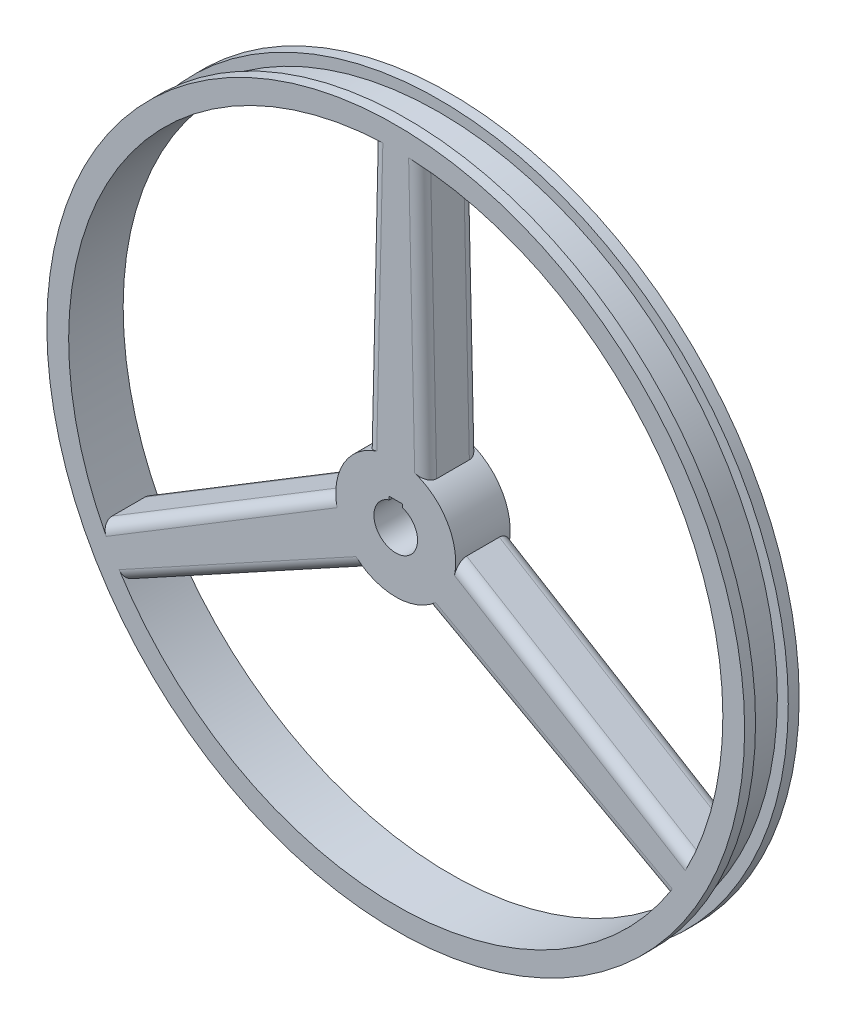
SolidWorks part; units mm, degrees
ref_plane "前视基准面" through (0, 0, 0) normal (0, 0, 1) x (1, 0, 0)
ref_plane "上视基准面" through (0, 0, 0) normal (0, 1, 0) x (1, 0, 0)
ref_plane "右视基准面" through (0, 0, 0) normal (1, 0, 0) x (0, 0, -1)
sketch "草图1" plane through (0, 0, 0) normal (0, 0, 1) x (1, 0, 0)
  circle A0 centre (0, 0) radius 320
  circle A1 centre (0, 0) radius 300
  dimension "D1" = 600
  dimension "D2" = 640
extrude "凸台-拉伸1" add sketch "草图1" along normal blind 50
sketch "草图2" plane through (0, 0, 0) normal (0, 0, 1) x (1, 0, 0)
  circle A0 centre (0, 0) radius 55
  circle A2 centre (0, 0) radius 20
  dimension "D1" = 110
extrude "凸台-拉伸2" add sketch "草图2" along normal blind 50 separate body
sketch "草图3" plane through (0, 0, 0) normal (0, 0, 1) x (1, 0, 0)
  line L0 (-55, 0) -> (-270.0343, -130.6961)
  line L1 (47.6314, -27.5) -> (211.9575, -122.3737) construction
  line L2 (47.6314, -27.5) -> (229.4967, -132.5) construction
  line L3 (-47.6314, -27.5) -> (-211.0865, -121.8708) construction
  line L4 (0, 55) -> (0, 244.3916) construction
  line L5 (-27.5, -47.6314) -> (-248.2033, -168.5085)
  line L6 (-27.5, 47.6314) -> (-21.831, 299.2046)
  line L7 (27.5, 47.6314) -> (21.831, 299.2046)
  line L8 (55, 0) -> (270.0343, -130.6961)
  line L9 (27.5, -47.6314) -> (248.2033, -168.5085)
  circle A0 centre (0, 0) radius 300 construction
  circle A1 centre (0, 0) radius 55 construction
  circle A2 centre (0, 0) radius 55
  circle A3 centre (0, 0) radius 300
  point P26 (0, 0)
  dimension "D1" = 3
extrude "凸台-拉伸3" add sketch "草图3" along normal blind 50 contours L0 A3 L5 A2 | L9 A3 L8 A2 | L7 A3 L6 A2 region at (-148.5306, -85.7542, 0) region at (0, 171.5083, 0) region at (148.5306, -85.7542, 0)
fillet "圆角1" radius 10 12 edges at (162.5172, -65.348, 0) (-24.6655, 173.418, 50) (24.6655, 173.418, 50) (24.6655, 173.418, 0) (-137.8516, -108.07, 0) (-162.5172, -65.348, 0) (-162.5172, -65.348, 50) (-137.8516, -108.07, 50) (137.8516, -108.07, 50) (162.5172, -65.348, 50) (-24.6655, 173.418, 0) (137.8516, -108.07, 0)
sketch "草图5" plane through (0, 0, 0) normal (0, 1, 0) x (1, 0, 0)
  line L0 (-355.7855, -25) -> (341.1197, -25) construction
  line L1 (-320, -40) -> (-320, -10)
  line L2 (-320, 0) -> (-320, -50) construction
  line L3 (-320, -10) -> (-310, -10)
  line L4 (-310, -10) -> (-310, -40)
  line L5 (-320, -40) -> (-310, -40)
  line L6 (0, 49.2141) -> (0, -82.2918) construction
  point P9 (-310, -25)
  point P10 (-320, -25)
  dimension "D1" = 15
  dimension "D2" = 10
revolve "切除-旋转5" cut sketch "草图5" angle 360 about L6
sketch "草图6" plane through (0, 0, 0) normal (0, 1, 0) x (1, 0, 0)
  line L0 (0, 117.9182) -> (0, -109.8953) construction
  line L1 (-341.2649, -25) -> (340.5166, -25) construction
  line L2 (-6, 0) -> (-6, -50)
  line L3 (320, 0) -> (-320, 0) construction
  line L4 (-320, -50) -> (320, -50) construction
  line L5 (6, 0) -> (6, -50)
  line L6 (-6, 0) -> (6, 0)
  line L7 (-6, -50) -> (6, -50)
  dimension "D1" = 6
extrude "切除-拉伸1" cut sketch "草图6" along normal blind 22
